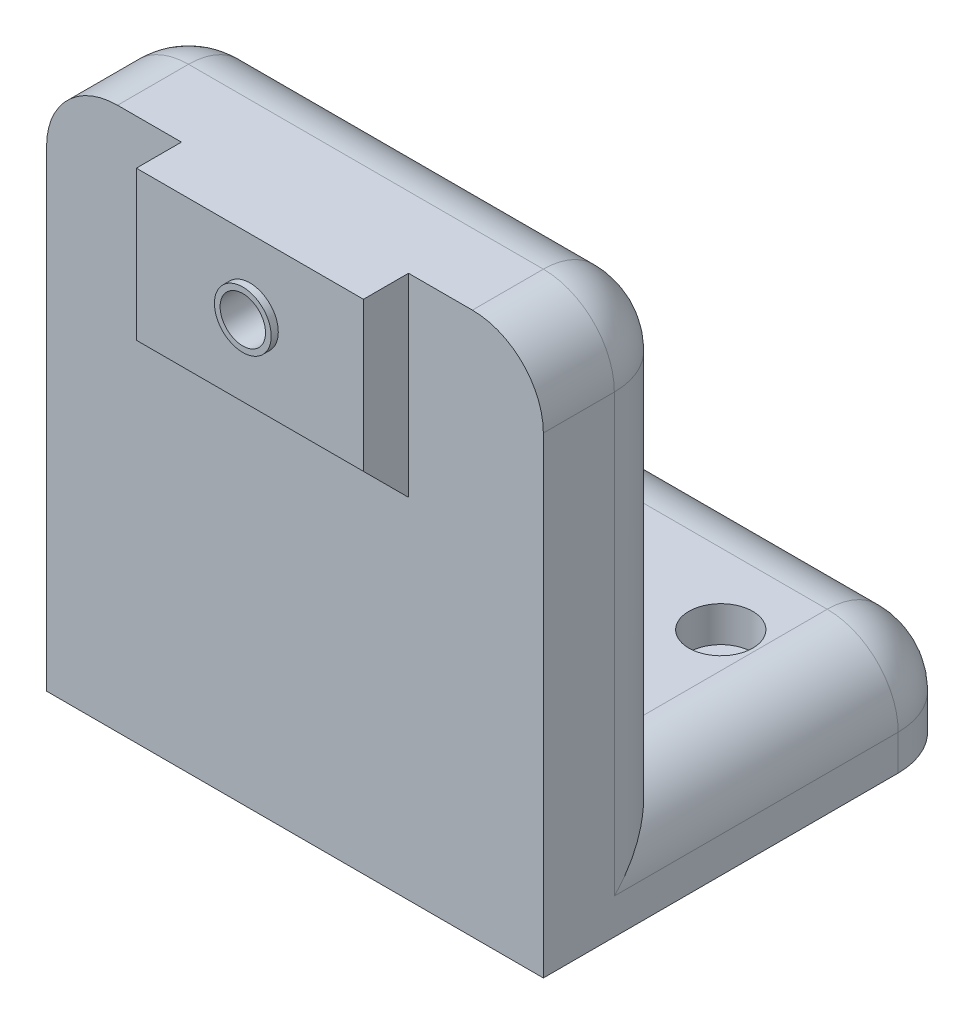
SolidWorks part; units mm, degrees
ref_plane "Front Plane" through (0, 0, 0) normal (0, 0, 1) x (1, 0, 0)
ref_plane "Top Plane" through (0, 0, 0) normal (0, 1, 0) x (1, 0, 0)
ref_plane "Right Plane" through (0, 0, 0) normal (1, 0, 0) x (0, 0, -1)
sketch "Sketch1" plane through (0, 0, 0) normal (0, 1, 0) x (1, 0, 0)
  line L1 (0, 0) -> (70, 0)
  line L2 (0, 0) -> (0, 60)
  line L3 (0, 60) -> (70, 60)
  line L4 (70, 0) -> (70, 60)
  dimension "D1" = 60
  dimension "D2" = 70
extrude "Boss-Extrude1" add sketch "Sketch1" along normal blind 15
sketch "Sketch2" plane through (0, 15, 0) normal (0, 1, 0) x (1, 0, 0)
  line L0 (70, 0) -> (70, 60) construction
  line L1 (0, 0) -> (70, 0)
  line L2 (0, 0) -> (0, 20)
  line L3 (0, 20) -> (70, 20)
  line L4 (70, 0) -> (70, 20)
  dimension "D1" = 20
extrude "Boss-Extrude2" add sketch "Sketch2" along normal blind 61.5
sketch "Sketch3" plane through (0, 0, 0) normal (0, 0, 1) x (1, 0, 0)
  line L0 (35, 76.5) -> (35, 0) construction
  line L1 (0, 76.5) -> (70, 76.5) construction
  line L2 (0, 0) -> (70, 0) construction
  circle A0 centre (35, 66.5) radius 3.2
  dimension "D1" = 66.5
  dimension "D2" = 6.4
extrude "Cut-Extrude1" cut sketch "Sketch3" against normal blind 10
sketch "Sketch5" plane through (0, 15, 0) normal (0, 1, 0) x (1, 0, 0)
  line L0 (0, 40) -> (70, 40) construction
  line L1 (0, 60) -> (0, 20) construction
  line L2 (70, 20) -> (70, 60) construction
  circle A0 centre (15, 40) radius 1.9
  circle A1 centre (35, 40) radius 1.9
  circle A2 centre (55, 40) radius 1.9
  dimension "D1" = 3
  dimension "D3" = 3.8
  dimension "D2" = 35
  dimension "D4" = 20
extrude "Cut-Extrude2" cut sketch "Sketch5" against normal through all
sketch "Sketch6" plane through (0, 15, 0) normal (0, 1, 0) x (1, 0, 0)
  circle A0 centre (15, 40) radius 4.5
  circle A1 centre (35, 40) radius 4.5
  circle A2 centre (55, 40) radius 4.5
  dimension "D1" = 9
extrude "Cut-Extrude3" cut sketch "Sketch6" against normal blind 5
fillet "Fillet1" radius 10 10 edges at (0, 7.5, -60) (70, 7.5, -60) (35, 15, -60) (70, 45.75, -20) (70, 15, -40) (0, 15, -40) (0, 45.75, -20) (0, 76.5, -10) (70, 76.5, -10) (35, 76.5, -20)
sketch "Sketch7" plane through (0, 0, 0) normal (0, 0, 1) x (1, 0, 0)
  line L1 (19, 76.5) -> (51, 76.5)
  line L2 (19, 76.5) -> (19, 56.5)
  line L3 (19, 56.5) -> (51, 56.5)
  line L4 (51, 76.5) -> (51, 56.5)
  line L5 (19, 76.5) -> (51, 56.5) construction
  line L6 (19, 56.5) -> (51, 76.5) construction
  circle A1 centre (35, 66.5) radius 3.2
  point P0 (35, 66.5)
  dimension "D1" = 32
  dimension "D3" = 6.4
  dimension "D2" = 20
extrude "Boss-Extrude3" add sketch "Sketch7" along normal blind 6.35
chamfer "Chamfer1" distance 7.35 angle 45 1 edges at (35, 56.5, 0)
sketch "Sketch8" plane through (0, 0, 6.35) normal (0, 0, 1) x (1, 0, 0)
  circle A0 centre (35, 66.5) radius 3.2
  circle A1 centre (35, 66.5) radius 4
  dimension "D1" = 8
  dimension "D2" = 6.4
extrude "Boss-Extrude4" add sketch "Sketch8" along normal blind 1
